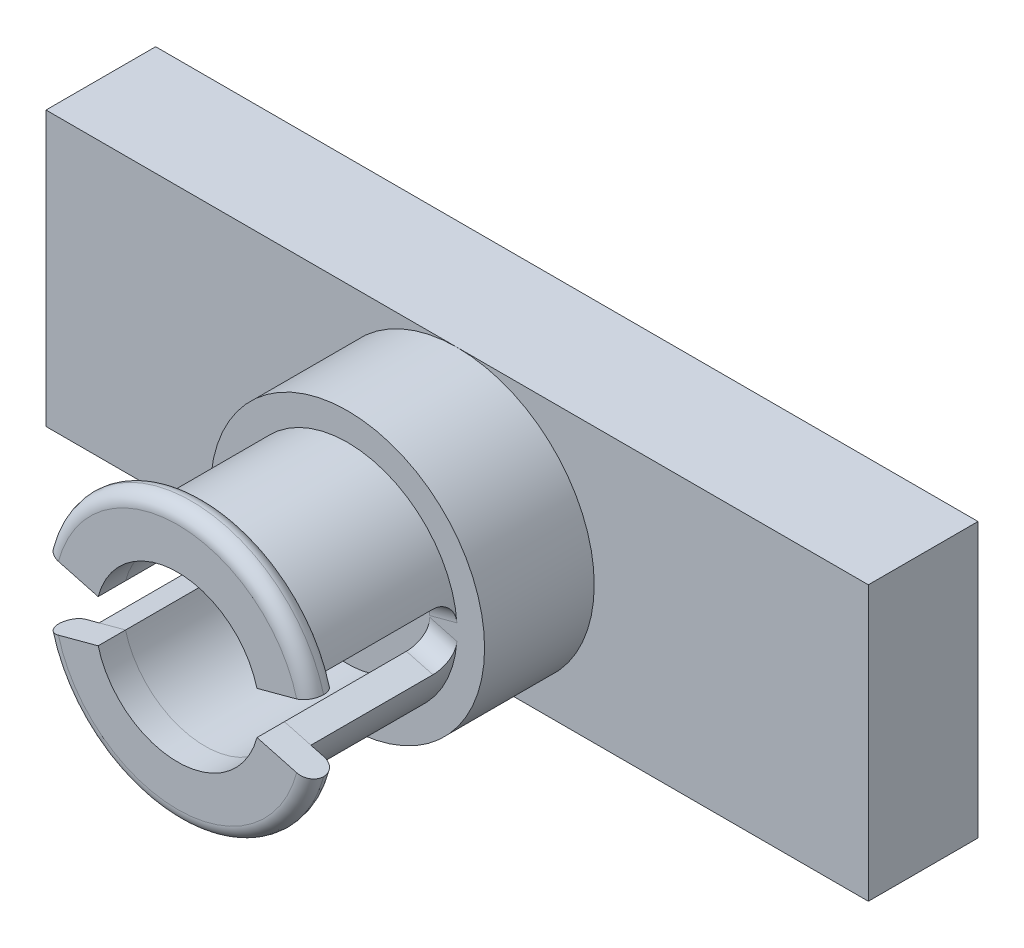
SolidWorks part; units mm, degrees
ref_plane "Front Plane" through (0, 0, 0) normal (0, 0, 1) x (1, 0, 0)
ref_plane "Top Plane" through (0, 0, 0) normal (0, 1, 0) x (1, 0, 0)
ref_plane "Right Plane" through (0, 0, 0) normal (1, 0, 0) x (0, 0, -1)
sketch "Sketch1" plane through (0, -120.0955, 0) normal (0, 1, 0) x (1, 0, 0)
  line L15 (21.8744, -117.0241) -> (51.8744, -117.0241)
  line L16 (21.8744, -117.0241) -> (21.8744, -121.0241)
  line L17 (21.8744, -121.0241) -> (51.8744, -121.0241)
  line L18 (51.8744, -117.0241) -> (51.8744, -121.0241)
  dimension "D1" = 4
  dimension "D2" = 30
extrude "Boss-Extrude1" add sketch "Sketch1" along normal blind 10 contours L16 L17 L18 L15
sketch "Sketch2" plane through (0, 0, 121.0241) normal (0, 0, 1) x (1, 0, 0)
  line L0 (21.8744, -110.0955) -> (51.8744, -110.0955) construction
  line L1 (21.8744, -110.0955) -> (21.8744, -120.0955) construction
  circle A0 centre (36.8744, -115.0955) radius 4
  circle A1 centre (36.8744, -115.0955) radius 5
  point P4 (36.8744, -110.0955)
  point P7 (21.8744, -115.0955)
extrude "Boss-Extrude2" add sketch "Sketch2" along normal blind 4 contours A0 | A1 A0
sketch "Sketch3" plane through (0, 0, 125.0241) normal (0, 0, 1) x (1, 0, 0)
  line L0 (32.8744, -115.0955) -> (40.8744, -115.0955)
  line L1 (33.0107, -116.1307) -> (40.7381, -114.0602)
  line L2 (33.0107, -114.0602) -> (40.7381, -116.1307)
  circle A0 centre (36.8744, -115.0955) radius 4
  circle A1 centre (36.8744, -115.0955) radius 5 construction
  circle A2 centre (36.8744, -115.0955) radius 3
  dimension "D1" = 15
  dimension "D2" = 15
extrude "Boss-Extrude3" add sketch "Sketch3" along normal blind 5.2 contours A2 L1 A0 L2 | A2 L1 A0 L2
ref_plane "Plane1" through (0, 0, 130.2241) normal (0, 0, 1) x (1, 0, 0)
sketch "Sketch5" plane through (0, 0, 130.2241) normal (0, 0, 1) x (1, 0, 0)
  line L0 (33.9766, -115.8719) -> (33.0107, -116.1307) construction
  line L1 (40.7381, -116.1307) -> (39.7722, -115.8719) construction
  line L2 (39.7722, -114.319) -> (40.7381, -114.0602) construction
  line L3 (33.0107, -114.0602) -> (33.9766, -114.319) construction
  line L4 (33.9766, -115.8719) -> (33.0107, -116.1307)
  line L5 (40.7381, -116.1307) -> (39.7722, -115.8719)
  line L6 (39.7722, -114.319) -> (40.7381, -114.0602)
  line L7 (33.0107, -114.0602) -> (33.9766, -114.319)
  line L8 (40.7381, -116.1307) -> (41.704, -116.3896)
  line L9 (41.704, -116.3896) -> (32.0448, -113.8014)
  line L10 (33.0107, -116.1307) -> (32.0448, -116.3896)
  line L11 (32.0448, -116.3896) -> (41.704, -113.8014)
  arc A0 (33.9766, -115.8719) -> (39.7722, -115.8719) centre (36.8744, -115.0955) ccw construction
  arc A2 (39.7722, -114.319) -> (33.9766, -114.319) centre (36.8744, -115.0955) ccw construction
  arc A4 (33.9766, -115.8719) -> (39.7722, -115.8719) centre (36.8744, -115.0955) ccw
  arc A6 (39.7722, -114.319) -> (33.9766, -114.319) centre (36.8744, -115.0955) ccw
  circle A8 centre (36.8744, -115.0955) radius 5
extrude "Boss-Extrude5" add sketch "Sketch5" along normal blind 1 separate body contours L11 A8 L9 L7 A6 L6 | L10 A8 L8 L5 A4 L4
fillet "Fillet2" radius 0.75 4 edges at (40.2552, -114.1896, 125.0241) (33.4937, -114.1896, 125.0241) (40.2552, -116.0013, 125.0241) (33.4937, -116.0013, 125.0241)
fillet "Fillet3" radius 0.5 2 edges at (36.8744, -110.0955, 130.2241) (36.8744, -110.0955, 131.2241)
fillet "Fillet4" radius 0.5 2 edges at (36.8744, -120.0955, 130.2241) (36.8744, -120.0955, 131.2241)
